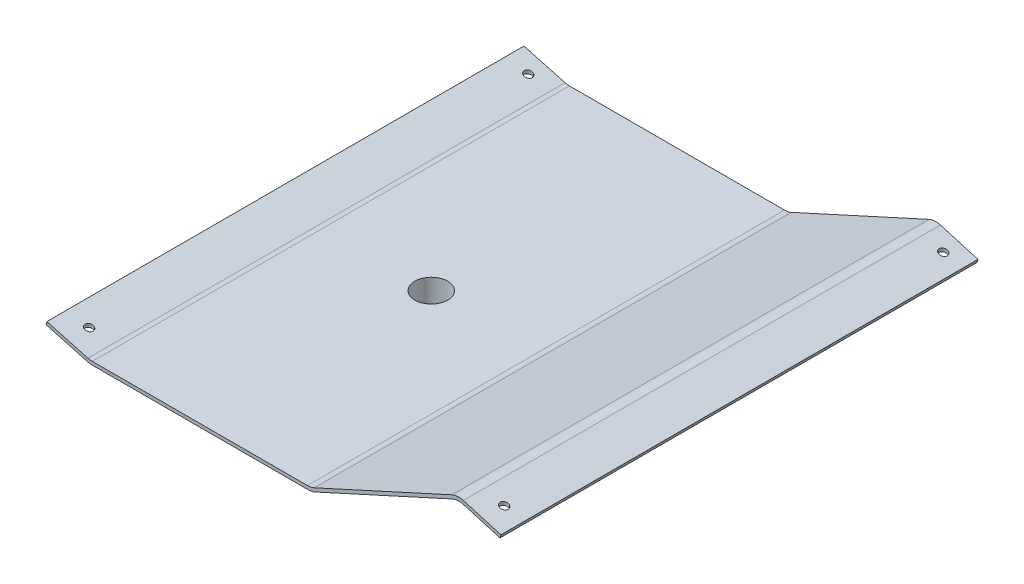
SolidWorks part; units mm, degrees
ref_plane "Front" through (0, 0, 0) normal (0, 0, 1) x (1, 0, 0)
ref_plane "Top" through (0, 0, 0) normal (0, 1, 0) x (1, 0, 0)
ref_plane "Right" through (0, 0, 0) normal (1, 0, 0) x (0, 0, -1)
sketch "Sketch1" plane through (0, 0, 0) normal (0, 0, 1) x (1, 0, 0)
  line L0 (0, 0) -> (-135, 0)
  line L1 (-135, 0) -> (-135, 7.5) construction
  line L2 (-135, 0) -> (-161.5335, 7.2266)
  line L3 (-135, 7.5) -> (-162.6224, 7.5) construction
  line L4 (0, 0) -> (0, 40.4448) construction
  line L5 (0, 0) -> (88.7157, 40.4448)
  line L6 (88.7157, 40.4448) -> (88.7157, 32.9448) construction
  line L7 (88.7157, 40.4448) -> (114.4218, 32.9448)
  line L8 (88.5623, 42.5729) -> (114.982, 34.8648)
  line L9 (-0.4344, 2) -> (88.5623, 42.5729)
  line L10 (-0.4344, 2) -> (-134.7325, 2)
  line L11 (-134.7325, 2) -> (-161.0079, 9.1563)
  line L12 (114.982, 34.8648) -> (114.4218, 32.9448)
  line L13 (-161.0079, 9.1563) -> (-161.5335, 7.2266)
  line L14 (0, 40.4448) -> (95.8564, 40.4448) construction
  line L15 (88.7157, 32.9448) -> (114.4218, 32.9448) construction
extrude "Boss-Extrude1" add sketch "Sketch1" along normal blind 290
sketch "Sketch2" plane through (0, 2, 0) normal (0, 1, 0) x (1, 0, 0)
  line L0 (-67.5835, 0) -> (-67.5835, -290) construction
  line L1 (-0.4344, 0) -> (-134.7325, 0) construction
  line L2 (-0.4344, -290) -> (-134.7325, -290) construction
  line L3 (-0.4344, -149.7695) -> (-134.7325, -149.7695) construction
  line L4 (-0.4344, -290) -> (-0.4344, 0) construction
  line L5 (-134.7325, -290) -> (-134.7325, 0) construction
  circle A0 centre (-67.5835, -149.7695) radius 60
extrude "Boss-Extrude2" add sketch "Sketch2" against normal blind 5
dome "Dome1" faces to dome 1 distance 30 reverse direction no elliptical dome no face at (-67.5835, -3, 209.7695) parameters "D1"=30
fillet "Fillet1" radius 10 1 edges at (-67.5835, -3, 209.7695)
sketch "Sketch3" plane through (0, 2, 0) normal (0, 1, 0) x (1, 0, 0)
  circle A0 centre (-67.5835, -149.7695) radius 10
extrude "Cut-Extrude1" cut sketch "Sketch3" against normal through all
fillet "Fillet2" radius 10 2 edges at (88.5623, 42.5729, 145) (88.7157, 40.4448, 145)
fillet "Fillet3" radius 10 4 edges at (-135, 0, 145) (0, 0, 145) (-134.7325, 2, 145) (-0.4344, 2, 145)
sketch "Sketch4" plane through (0, 0, 0) normal (0, 0, 1) x (1, 0, 0)
  line L0 (-134.9882, 0.0883) -> (120.4902, 0.0883) construction
  line L1 (120.4902, 0.0883) -> (-168.7248, 0.0883) construction
  line L2 (103.3525, 36.1744) -> (103.3525, 0.0883) construction
  line L3 (92.2832, 39.4039) -> (114.4218, 32.9448) construction
  line L4 (-148.912, 3.789) -> (-148.912, 0.0883) construction
  line L5 (-161.5335, 7.2266) -> (-136.2904, 0.3515) construction
  arc A0 (-136.2904, 0.3515) -> (-133.6626, 0) centre (-133.6626, 10) ccw construction
sketch "Sketch5" plane through (-9.3225, -34.2291, 0) normal (-0.2628, -0.9649, 0) x (0.9649, -0.2628, 0)
  line L4 (-131.5928, 0) -> (-131.5928, 290) construction
  line L5 (-157.7554, 290) -> (-131.5928, 290) construction
  line L6 (-131.5928, 290) -> (-157.7554, 263.8374) construction
  line L7 (-157.7554, 290) -> (-131.5928, 263.8374) construction
  line L8 (-157.7554, 290) -> (129.4306, 290) construction
  line L9 (-144.6741, 290) -> (-144.6741, 0) construction
  line L10 (-14.1624, 290) -> (-14.1624, 0) construction
  line L11 (-157.7554, 145) -> (129.4306, 145) construction
  line L12 (-157.7554, 290) -> (-157.7554, 0) construction
  circle A0 centre (-144.6741, 276.9187) radius 2.42
  circle A1 centre (116.3493, 276.9187) radius 2.42
  circle A2 centre (-144.6741, 13.0813) radius 2.42
  circle A3 centre (116.3493, 13.0813) radius 2.42
  point P24 (116.3493, 13.0813)
sketch "Sketch7" plane through (17.8338, 61.1252, 0) normal (-0.2801, -0.96, 0) x (0.96, -0.2801, 0)
  line L4 (77.5533, 290) -> (77.5533, 0) construction
  line L5 (100.615, 290) -> (77.5533, 266.9384) construction
  line L6 (77.5533, 290) -> (100.615, 266.9384) construction
  line L7 (100.615, 145) -> (-163.3673, 145) construction
  line L8 (100.615, 290) -> (100.615, 0) construction
  circle A0 centre (89.0841, 278.4692) radius 2.42
  circle A1 centre (89.0841, 11.5308) radius 2.42
sketch "Sketch8" plane through (0, 0, 0) normal (0, 1, 0) x (1, 0, 0)
  line L0 (103.9127, -10.0187) -> (103.9127, -276.9187) construction
  line L1 (103.9127, -276.9187) -> (-148.3873, -276.9187) construction
  line L3 (-148.3873, -10.0187) -> (-148.3873, -276.9187) construction
  line L4 (-148.3873, -10.0187) -> (103.9127, -10.0187) construction
  circle A0 centre (-148.3873, -10.0187) radius 2.42
  circle A1 centre (103.9127, -10.0187) radius 2.42
  circle A2 centre (103.9127, -276.9187) radius 2.42
  circle A3 centre (-148.3873, -276.9187) radius 2.42
  dimension "D1" = 266.9
  dimension "D2" = 252.3
extrude "Cut-Extrude2" cut sketch "Sketch8" along normal blind 40
